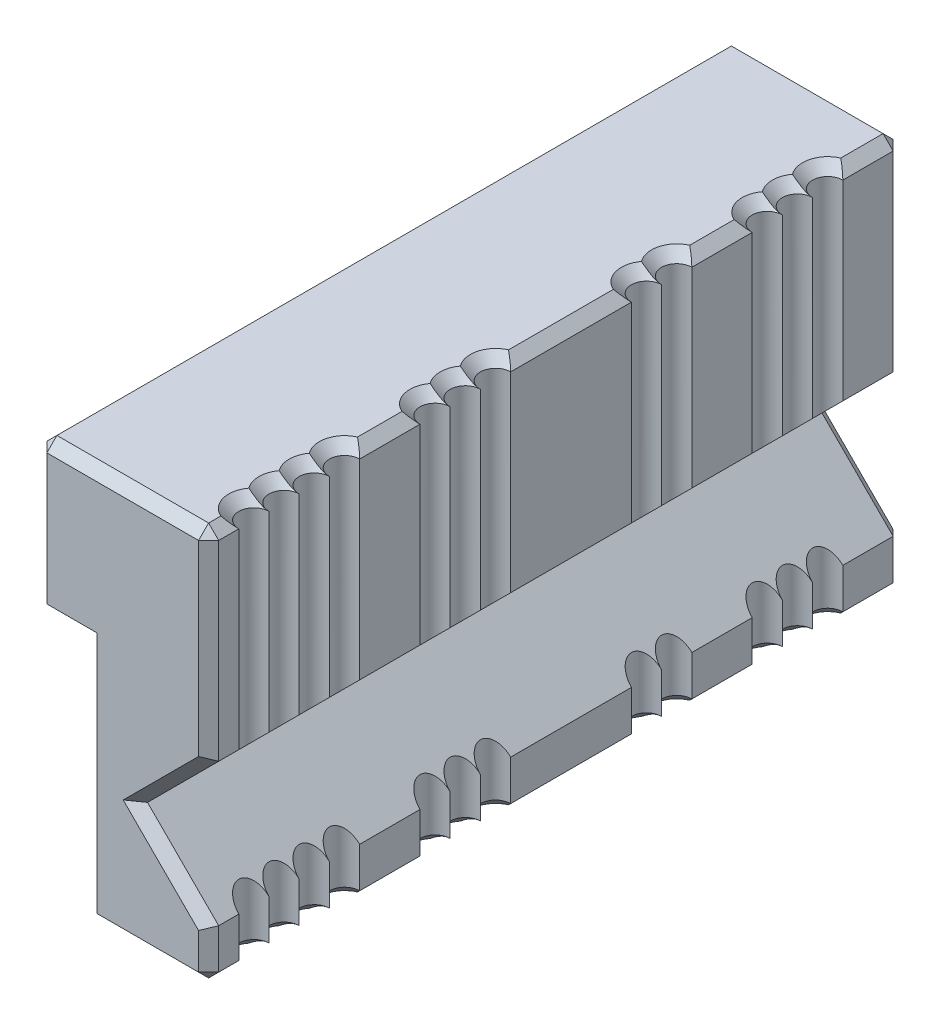
SolidWorks part; units mm, degrees
ref_plane "Front Plane" through (0, 0, 0) normal (0, 0, 1) x (1, 0, 0)
ref_plane "Top Plane" through (0, 0, 0) normal (0, 1, 0) x (1, 0, 0)
ref_plane "Right Plane" through (0, 0, 0) normal (1, 0, 0) x (0, 0, -1)
sketch "Sketch1" plane through (0, 0, 0) normal (0, 0, 1) x (1, 0, 0)
  line L0 (-7.0711, 0) -> (0, 7.0711)
  line L1 (0, 7.0711) -> (0, 27.0711)
  line L2 (0, 27.0711) -> (-17.0711, 27.0711)
  line L3 (-17.0711, 27.0711) -> (-17.0711, 12.0711)
  line L4 (-17.0711, 12.0711) -> (-12.0711, 12.0711)
  line L5 (-12.0711, 12.0711) -> (-12.0711, -12.0711)
  line L6 (-12.0711, -12.0711) -> (0, -12.0711)
  line L7 (0, -12.0711) -> (0, -7.0711)
  line L8 (0, -7.0711) -> (-7.0711, 0)
  circle A0 centre (0, 0) radius 5 construction
  dimension "D1" = 10
  dimension "D2" = 0
  dimension "D3" = 5
  dimension "D4" = 15
  dimension "D5" = 5
  dimension "D6" = 5
  dimension "D7" = 20
extrude "Boss-Extrude1" add sketch "Sketch1" along normal blind 69
sketch "Sketch2" plane through (0, 27.0711, 0) normal (0, 1, 0) x (1, 0, 0)
  circle A0 centre (0, -7.5) radius 1.5
  dimension "D1" = 3
  dimension "D2" = 6
extrude "Cut-Extrude1" cut sketch "Sketch2" against normal through all
pattern_linear "LPattern2" count 20 spacing 3 along (0, 0, 1) skipping (3, 0), (4, 0), (7, 0), (8, 0), (9, 0), (10, 0), (14, 0), (15, 0) of "Cut-Extrude1"
chamfer "Chamfer2" distance 1 angle 45 55 edges at (0, 27.0711, 67.5) (-1.5, 27.0711, 25.5) (-1.5, 27.0711, 22.5) (-1.5, 27.0711, 13.5) (-1.5, 27.0711, 10.5) (-1.5, 27.0711, 7.5) (0, 27.0711, 3) (-1.5, -12.0711, 25.5) (-1.5, -12.0711, 22.5) (-1.5, -12.0711, 13.5) (-1.5, -12.0711, 10.5) (-1.5, -12.0711, 7.5) (0, -12.0711, 3) (0, -12.0711, 67.5) (0, -9.5711, 69) (-6.0355, -12.0711, 69) (-14.5711, 12.0711, 69) (-3.5355, -3.5355, 69) (-3.5355, 3.5355, 69) (0, 17.0711, 69) (-8.5355, 27.0711, 69) (-3.5355, 3.5355, 0) (0, 17.0711, 0) (-8.5355, 27.0711, 0) (-17.0711, 27.0711, 34.5) (-17.0711, 19.5711, 69) (-17.0711, 12.0711, 34.5) (-17.0711, 19.5711, 0) (-14.5711, 12.0711, 0) (-3.5355, -3.5355, 0) (0, -9.5711, 0) (-6.0355, -12.0711, 0) (-12.0711, 0, 69) (-12.0711, -12.0711, 34.5) (-12.0711, 0, 0) (0, 27.0711, 18) (0, 27.0711, 33) (0, -12.0711, 18) (0, -12.0711, 33) (-1.5, 27.0711, 43.5) (0, 27.0711, 51) (-1.5, 27.0711, 55.5) (-1.5, 27.0711, 64.5) (-1.5, -12.0711, 43.5) (0, -12.0711, 51) (-1.5, -12.0711, 55.5) (-1.5, -12.0711, 64.5) (-1.5, 27.0711, 40.5) (-1.5, 27.0711, 46.5) (-1.5, 27.0711, 58.5) (-1.5, 27.0711, 61.5) (-1.5, -12.0711, 58.5) (-1.5, -12.0711, 46.5) (-1.5, -12.0711, 40.5) (-1.5, -12.0711, 61.5)
equation "\"Drill Bit OD\"=3"
equation "\"Shaft OD\"=10"
equation "\"Length\"= 100"
equation "\"Number of Holes\"= 10"
equation "\"Face Gap\"= 0"
equation "\"Shaft OD Oversize\"= 0.4"
equation "\"Drill Bit Hole Oversize\"= 0.4"
equation "\"D1@Sketch1\"=\"Shaft OD\""
equation "\"D2@Sketch1\"=\"Face Gap\" / 2"
equation "\"D1@Boss-Extrude1\"=(\"Number of Holes\" + 1.5) * \"Drill Bit OD\" * 2"
equation "\"D1@Sketch2\"=\"Drill Bit OD\""
equation "\"D3@LPattern2\"=\"Drill Bit OD\""
equation "\"D1@LPattern2\"=\"Number of Holes\"*2"
equation "\"D2@Sketch2\"=\"Drill Bit OD\"*2"
